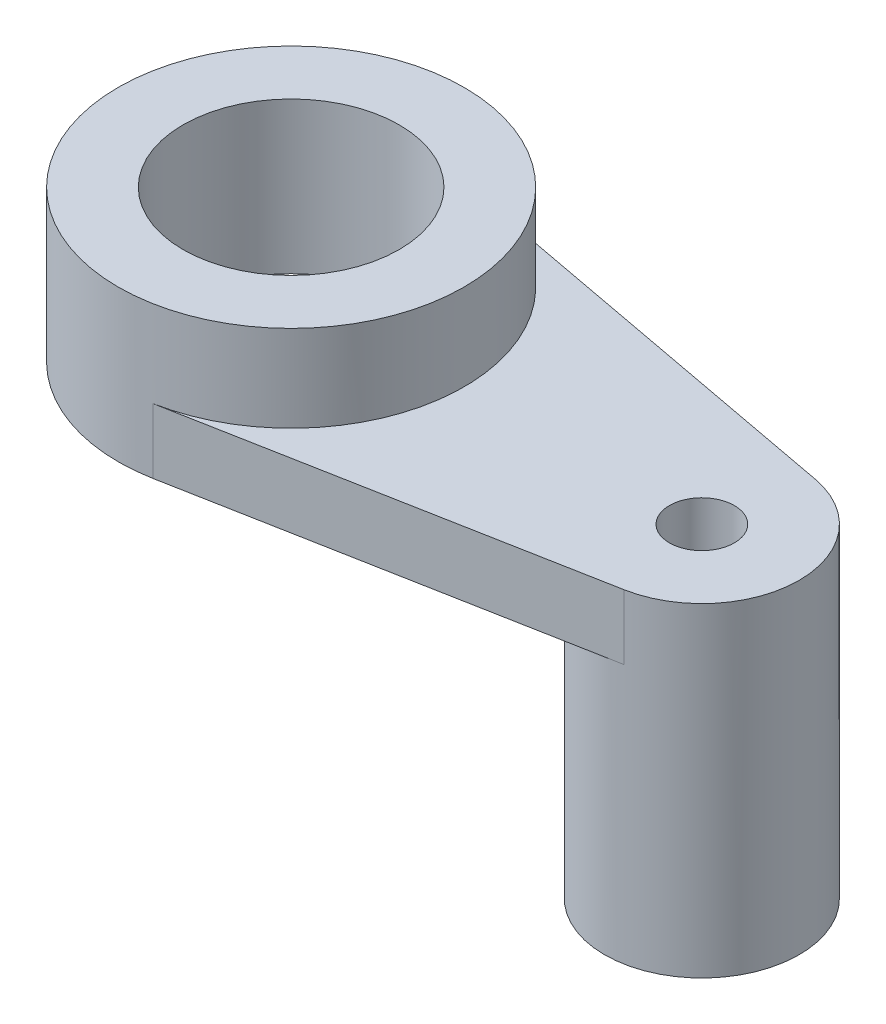
SolidWorks part; units mm, degrees
ref_plane "Front Plane" through (0, 0, 0) normal (0, 0, 1) x (1, 0, 0)
ref_plane "Top Plane" through (0, 0, 0) normal (0, 1, 0) x (1, 0, 0)
ref_plane "Right Plane" through (0, 0, 0) normal (1, 0, 0) x (0, 0, -1)
other "Configuration Table"
sketch "Sketch1" plane through (0, 0, 0) normal (0, 1, 0) x (1, 0, 0)
  line L0 (2.9474, 15.7262) -> (39.6579, 8.846)
  line L1 (-55, 0) -> (55, 0) construction
  line L2 (2.9474, -15.7262) -> (39.6579, -8.846)
  circle A0 centre (0, 0) radius 16
  circle A1 centre (38, 0) radius 9
  circle A2 centre (38, 0) radius 3
  circle A3 centre (0, 0) radius 10
  point P13 (0, 0)
  point P14 (0, 0)
  dimension "D1" = 38
  dimension "D2" = 18
  dimension "D3" = 6
  dimension "D4" = 20
  dimension "D5" = 6
extrude "Boss-Extrude1" add sketch "Sketch1" along normal blind 6 contours A1 L0 A0 L2 | A0 A3 | A1 A2 region at (21.925, 0, 0) region at (11.9635, 0, -9.9296) region at (44.7295, 0, -5.5854)
extrude "Boss-Extrude2" add sketch "Sketch1<3>" along normal blind 14 contours A0 A3 region at (11.9635, 0, -9.9296)
sketch "Sketch1<3>" plane through (0, 0, 0) normal (0, 1, 0) x (1, 0, 0) same geometry as "Sketch1"
extrude "Boss-Extrude3" add sketch "Sketch1<4>" against normal blind 24 contours A1 A2 region at (44.7295, 0, -5.5854)
sketch "Sketch1<4>" plane through (0, 0, 0) normal (0, 1, 0) x (1, 0, 0) same geometry as "Sketch1"
equation "\"GAUGE\"= SWITCH ( \"Thickness\" < 0.9 , 0 , \"Thickness\" < 1.1 , 20 , \"Thickness\" < 1.6 , 16 , \"Thickness\" < 2.1 , 14 , \"Thickness\" < 3.1 , 11 , \"Thickness\" < 4.8 , 7 , \"Thickness\" > 4.8 , 0 )"
